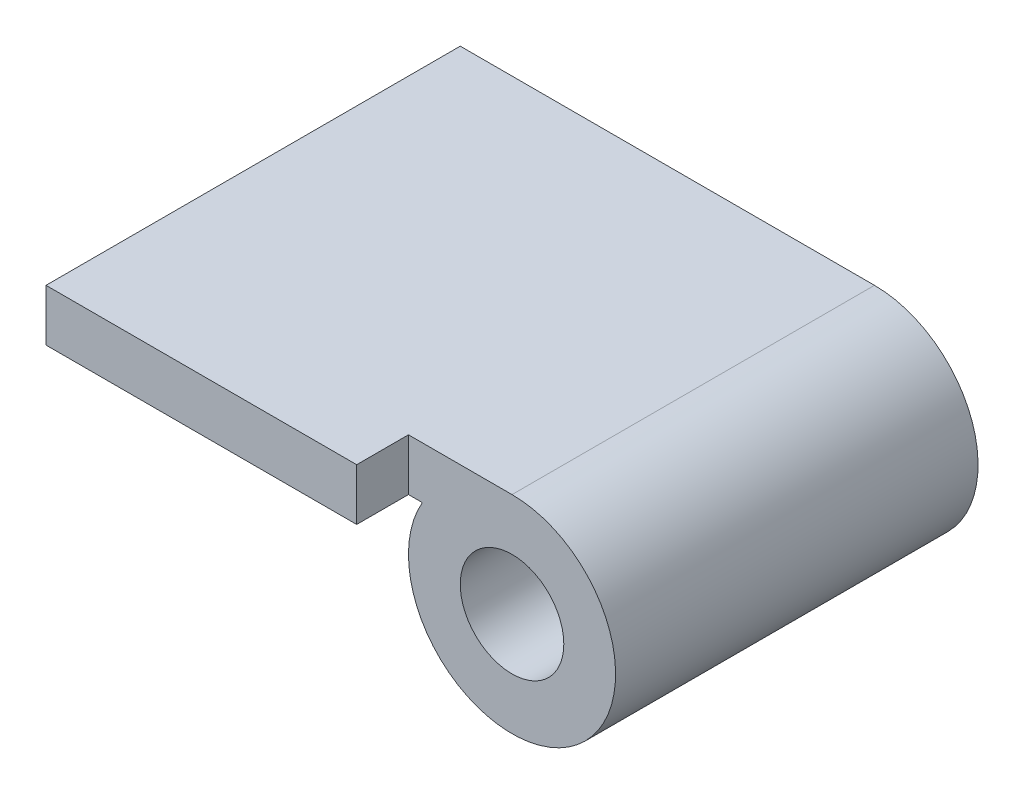
SolidWorks part; units mm, degrees
ref_plane "Front Plane" through (0, 0, 0) normal (0, 0, 1) x (1, 0, 0)
ref_plane "Top Plane" through (0, 0, 0) normal (0, 1, 0) x (1, 0, 0)
ref_plane "Right Plane" through (0, 0, 0) normal (1, 0, 0) x (0, 0, -1)
sketch "Sketch1" plane through (0, 0, 0) normal (0, 0, 1) x (1, 0, 0)
  line L1 (0, 3.175) -> (-25.4, 3.175)
  line L2 (-25.4, 3.175) -> (-25.4, 6.35)
  line L3 (-25.4, 6.35) -> (0, 6.35)
  circle A0 centre (0, 0) radius 6.35
  circle A1 centre (0, 0) radius 3.175
  point P12 (0, 0)
  dimension "D1" = 6.35
  dimension "D2" = 12.7
  dimension "D3" = 25.4
extrude "Boss-Extrude1" add sketch "Sketch1" along normal blind 25.4 contours A0 L3 L2 L1 | A1 A0 region at (-3.0852, 5.3437, 0) region at (-14.613, 4.8143, 0)
sketch "Sketch2" plane through (0, 0, 25.4) normal (0, 0, 1) x (1, 0, 0)
  line L0 (-25.4, 6.35) -> (0, 6.35) construction
  line L1 (6.35, -6.35) -> (-6.35, -6.35)
  line L2 (6.35, -6.35) -> (6.35, 6.35)
  line L3 (6.35, 6.35) -> (-6.35, 6.35)
  line L4 (-6.35, -6.35) -> (-6.35, 6.35)
  line L5 (6.35, -6.35) -> (-6.35, 6.35) construction
  line L6 (6.35, 6.35) -> (-6.35, -6.35) construction
  arc A0 (-5.4993, 3.175) -> (0, 6.35) centre (0, 0) ccw construction
  point P0 (0, 0)
extrude "Cut-Extrude1" cut sketch "Sketch2" against normal blind 3.175
